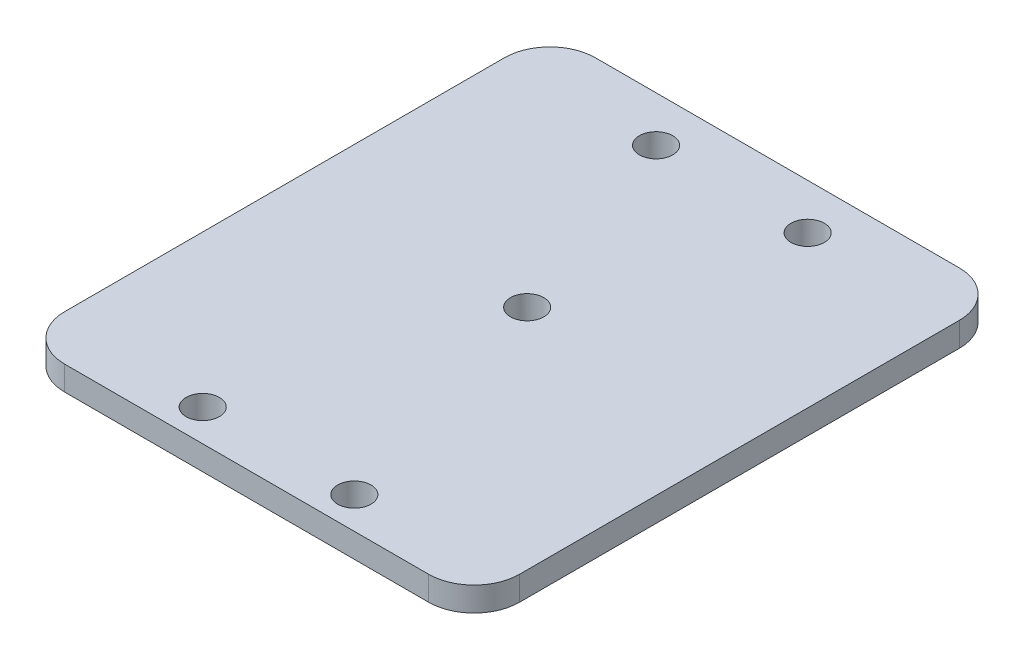
SolidWorks part; units mm, degrees
ref_plane "Front Plane" through (0, 0, 0) normal (0, 0, 1) x (1, 0, 0)
ref_plane "Top Plane" through (0, 0, 0) normal (0, 1, 0) x (1, 0, 0)
ref_plane "Right Plane" through (0, 0, 0) normal (1, 0, 0) x (0, 0, -1)
sketch "Sketch1" plane through (0, 0, 0) normal (0, 1, 0) x (1, 0, 0)
  line L0 (-15, 17.5) -> (15, -17.5) construction
  line L1 (-15, 17.5) -> (15, 17.5)
  line L2 (-15, 17.5) -> (-15, -17.5)
  line L3 (-15, -17.5) -> (15, -17.5)
  line L4 (15, 17.5) -> (15, -17.5)
  point P4 (0, 0)
  dimension "D1" = 35
  dimension "D2" = 30
extrude "Boss-Extrude1" add sketch "Sketch1" along normal blind 1.6
sketch "Sketch4" plane through (0, 0, 0) normal (0, -1, 0) x (1, 0, 0)
  line L0 (0, -0.88) -> (0, 0.88) construction
  line L1 (-15, 17.5) -> (15, 17.5) construction
  circle A1 centre (0, -9.5) radius 0.75
  point P1 (-3.8354, -11.6829)
  point P3 (0, 0)
  dimension "D1" = 1.5
  dimension "D2" = 27
sketch "Sketch5" plane through (0, 0, 0) normal (0, -1, 0) x (1, 0, 0)
  line L2 (15, -17.5) -> (-15, -17.5) construction
  line L3 (-15, 17.5) -> (15, 17.5) construction
  line L12 (7, 17.5) -> (3, 17.5)
  line L13 (7, -17.5) -> (7, 17.5)
  line L14 (3, -17.5) -> (7, -17.5)
  line L15 (3, -7) -> (3, -17.5)
  line L16 (-0.5, -4.5) -> (0.5, -4.5)
  line L17 (-3, -17.5) -> (-3, -7)
  line L18 (-7, -17.5) -> (-3, -17.5)
  line L19 (-7, 17.5) -> (-7, -17.5)
  line L20 (-3, 17.5) -> (-7, 17.5)
  line L21 (-3, 5) -> (-3, 17.5)
  line L22 (0.5, 2.5) -> (-0.5, 2.5)
  line L23 (3, 17.5) -> (3, 5)
  line L24 (7, 17.5) -> (3, 17.5)
  line L25 (7, -17.5) -> (7, 17.5)
  line L26 (3, -17.5) -> (7, -17.5)
  line L27 (3, -7) -> (3, -17.5)
  line L28 (-0.5, -4.5) -> (0.5, -4.5)
  line L29 (-3, -17.5) -> (-3, -7)
  line L30 (-7, -17.5) -> (-3, -17.5)
  line L31 (-7, 17.5) -> (-7, -17.5)
  line L32 (-3, 17.5) -> (-7, 17.5)
  line L33 (-3, 5) -> (-3, 17.5)
  line L34 (0.5, 2.5) -> (-0.5, 2.5)
  line L35 (3, 17.5) -> (3, 5)
  arc A4 (3, -7) -> (0.5, -4.5) centre (0.5, -7) ccw
  arc A5 (-0.5, -4.5) -> (-3, -7) centre (-0.5, -7) ccw
  arc A6 (-3, 5) -> (-0.5, 2.5) centre (-0.5, 5) ccw
  arc A7 (0.5, 2.5) -> (3, 5) centre (0.5, 5) ccw
  arc A8 (3, -7) -> (0.5, -4.5) centre (0.5, -7) ccw
  arc A9 (-0.5, -4.5) -> (-3, -7) centre (-0.5, -7) ccw
  arc A10 (-3, 5) -> (-0.5, 2.5) centre (-0.5, 5) ccw
  arc A11 (0.5, 2.5) -> (3, 5) centre (0.5, 5) ccw
  dimension "D1" = 0
extrude "Cut-Extrude3" cut sketch "Sketch5" against normal blind 0.001
hole_wizard "M2 Clearance Hole1" positions "Sketch2" profile "Sketch3" hole size "M2" standard "ANSI Metric"
sketch "Sketch2" plane through (0, 1.6, 0) normal (0, 1, 0) x (1, 0, 0)
  line L1 (0, 17.5) -> (0, -17.5) construction
  line L2 (15, 17.5) -> (-15, 17.5) construction
  line L3 (-15, -17.5) -> (15, -17.5) construction
  line L5 (-5, 14.5) -> (-5, 17.5) construction
  line L7 (-5, -15.4) -> (-5, -17.5) construction
  line L8 (-15, 17.5) -> (-15, -17.5) construction
  line L9 (0, -2.5) -> (0, 4.5) construction
  line L12 (-0.5, 4.5) -> (0.5, 4.5) construction
  line L13 (0.5, -2.5) -> (-0.5, -2.5) construction
  point P0 (-5, 14.5)
  point P4 (-5, -15.4)
  point P27 (5, -15.4)
  point P29 (5, 14.5)
  point P52 (0, 1)
  dimension "D1" = 10
  dimension "D2" = 32
  dimension "D3" = 20
  dimension "D4" = 2.1
sketch "Sketch3" plane through (-5, 1.6, -14.5) normal (1, 0, 0) x (0, 0, 1)
  line L0 (0, 0) -> (0, 5.8609)
  line L1 (0, 5.8609) -> (1.1, 5.2)
  line L2 (1.1, 5.2) -> (1.1, 0)
  line L5 (1.1, 0) -> (0, 0)
  line L10 (0, 5.8609) -> (-1.1, 5.2) construction
  line L11 (0, -6.35) -> (0, 107.95) construction
  dimension "Hole Dia." = 2.2
  dimension "Hole Depth" = 5.2
  dimension "Drill Angle" = 118
mirror "Mirror1" [suppressed] about plane through (0, 0, 0) normal (1, 0, 0)
sketch "Sketch6" [suppressed] plane through (0, 1.6, 0) normal (0, 1, 0) x (1, 0, 0)
  line L1 (-15, 17.5) -> (-23, 17.5)
  line L2 (-15, 17.5) -> (-15, -17.5)
  line L3 (-15, -17.5) -> (-23, -17.5)
  line L4 (-23, 17.5) -> (-23, -17.5)
  dimension "D1" = 8
extrude "Boss-Extrude2" [suppressed] add sketch "Sketch6" against normal up to surface (1.6 mm away) up to face at (0, 0, -9.4941)
mirror "Mirror2" [suppressed] about plane through (0, 0, 0) normal (1, 0, 0)
sketch "Sketch7" [suppressed] plane through (0, 1.6, 0) normal (0, 1, 0) x (1, 0, 0)
  line L1 (-23, 17.5) -> (23, 17.5)
  line L2 (-23, 17.5) -> (-23, 37.5)
  line L3 (-23, 37.5) -> (23, 37.5)
  line L4 (23, 17.5) -> (23, 37.5)
  dimension "D1" = 20
extrude "Boss-Extrude3" [suppressed] add sketch "Sketch7" against normal up to surface (1.6 mm away) up to face at (0, 0, -9.4941)
chamfer "Chamfer1" [suppressed] distance 15 angle 30
chamfer "Chamfer2" [suppressed] distance 15 angle 30
fillet "Fillet1" [suppressed] radius 3
sketch "DXFalligners" [suppressed] plane through (0, 1.6, 0) normal (0, 1, 0) x (1, 0, 0)
  line L0 (-23, 21.6962) -> (-23, -14.5) construction
  line L1 (-20, -17.5) -> (20, -17.5) construction
  line L2 (23, 21.6962) -> (23, -14.5) construction
  point P0 (-23, -17.5)
  point P8 (23, -17.5)
fillet "Fillet2" radius 3 4 edges at (15, 0.8, 17.5) (-15, 0.8, 17.5) (-15, 0.8, -17.5) (15, 0.8, -17.5)
